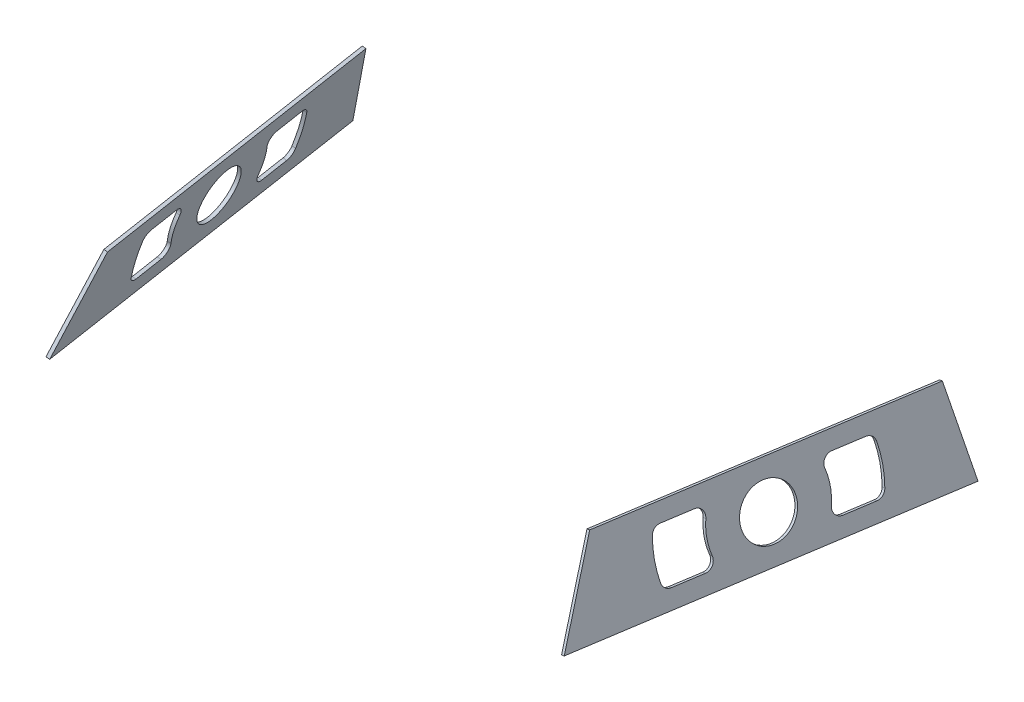
SolidWorks part; units mm, degrees
material "AISI 4130 Steel, normalized at 870C"
ref_plane "Front Plane" through (0, 0, 0) normal (0, 0, 1) x (1, 0, 0)
ref_plane "Top Plane" through (0, 0, 0) normal (0, 1, 0) x (1, 0, 0)
ref_plane "Right Plane" through (0, 0, 0) normal (1, 0, 0) x (0, 0, -1)
ref_plane "Plane1" through (-580.5935, 163.5796, 89.4113) normal (-0.9521, 0.2683, 0.1466) x (0.1411, -0.0398, 0.9892)
sketch "Sketch1" plane through (-580.5935, 163.5796, 89.4113) normal (-0.9521, 0.2683, 0.1466) x (0.1411, -0.0398, 0.9892)
  line L0 (1424.3171, 809.6189) -> (1417.4728, 759.2873)
  line L1 (1417.4728, 759.2873) -> (1634.8983, 768.4219)
  line L2 (1634.8983, 768.4219) -> (1609.6358, 817.4047)
  line L3 (1609.6358, 817.4047) -> (1424.3171, 809.6189)
  line L6 (1409.8147, 798.5353) -> (1433.754, 799.5411) construction
  line L7 (1581.1847, 765.6997) -> (1613.0162, 767.037) construction
  line L9 (1463.8222, 1100.131) -> (1891.0271, 271.7993) construction
  line L10 (1463.8222, 1100.131) -> (1356.2291, 308.913) construction
  line L11 (1591.981, 851.6367) -> (1429.116, 844.9085) construction
  point P4 (1411.0184, 806.0925)
  point P5 (1412.9086, 821.061)
  point P7 (1570.7525, 855.3408)
  point P12 (0, 0)
  point P13 (0, 0)
  point P14 (0, 0)
  point P20 (1510.5485, 848.2726)
  dimension "D1" = 50
  dimension "D2" = 35
extrude "Boss-Extrude1" add sketch "Sketch1" along normal blind 2 from offset 12.7
sketch "Sketch3" plane through (-580.5935, 163.5796, 89.4113) normal (-0.9521, 0.2683, 0.1466) x (0.1411, -0.0398, 0.9892)
  line L0 (1420.895, 784.4531) -> (1622.2671, 792.9133) construction
  line L1 (1424.3171, 809.6189) -> (1417.4728, 759.2873) construction
  line L2 (1634.8983, 768.4219) -> (1609.6358, 817.4047) construction
  line L3 (1516.9765, 813.5118) -> (1526.1856, 763.8546) construction
  line L4 (1609.6358, 817.4047) -> (1424.3171, 809.6189) construction
  line L5 (1417.4728, 759.2873) -> (1634.8983, 768.4219) construction
  circle A0 centre (1521.581, 788.6832) radius 15
  dimension "D1" = 30
extrude "Cut-Extrude4" cut sketch "Sketch3" along normal through all both and the other way through all contours A0
sketch "Sketch4" plane through (-594.5898, 167.523, 91.5668) normal (-0.9521, 0.2683, 0.1466) x (0.1423, -0.0358, 0.9892)
  line L0 (1488.1402, 796.0159) -> (1470.2119, 795.3368)
  line L1 (1489.2757, 766.0374) -> (1471.3474, 765.3583)
  line L2 (1560.3726, 798.7519) -> (1578.3009, 799.4309)
  line L3 (1561.5081, 768.7734) -> (1579.4364, 769.4524)
  line L4 (1612.9968, 810.7523) -> (1427.6475, 803.7317) construction
  line L5 (1489.2757, 766.0374) -> (1561.5081, 768.7734) construction
  line L6 (1420.5955, 753.4288) -> (1638.0568, 761.6656) construction
  line L7 (1488.1402, 796.0159) -> (1560.3726, 798.7519) construction
  arc A1 (1465.4536, 791.0627) -> (1466.2794, 769.2602) centre (1524.8241, 782.3946) ccw
  arc A2 (1556.4529, 774.9197) -> (1555.7968, 792.2407) centre (1524.8241, 782.3946) ccw
  arc A3 (1584.1947, 773.7265) -> (1583.3689, 795.5291) centre (1524.8241, 782.3946) ccw
  arc A4 (1579.4364, 769.4524) -> (1584.1947, 773.7265) centre (1579.2472, 774.4488) ccw
  arc A5 (1578.3009, 799.4309) -> (1583.3689, 795.5291) centre (1578.4902, 794.4345) cw
  arc A9 (1471.3474, 765.3583) -> (1466.2794, 769.2602) centre (1471.1581, 770.3547) cw
  arc A11 (1470.2119, 795.3368) -> (1465.4536, 791.0627) centre (1470.4011, 790.3404) ccw
  arc A12 (1493.1954, 789.8695) -> (1493.8515, 772.5486) centre (1524.8241, 782.3946) ccw
  arc A13 (1489.2757, 766.0374) -> (1493.8515, 772.5486) centre (1489.0865, 771.0338) ccw
  arc A14 (1493.1954, 789.8695) -> (1488.1402, 796.0159) centre (1488.3295, 791.0195) ccw
  arc A15 (1556.4529, 774.9197) -> (1561.5081, 768.7734) centre (1561.3188, 773.7698) ccw
  arc A16 (1555.7968, 792.2407) -> (1560.3726, 798.7519) centre (1560.5618, 793.7554) cw
  circle A20 centre (1524.8241, 782.3946) radius 15 construction
  point P0 (1466.6885, 807.4312)
  point P16 (1583.445, 769.6043)
  point P30 (1467.3388, 765.2065)
  point P36 (1466.2033, 795.185)
  dimension "D1" = 32.5
  dimension "D2" = 120
  dimension "D5" = 5
  dimension "D6" = 32.5
  dimension "D8" = 5
  dimension "D7" = 5
  dimension "D9" = 5
  dimension "D10" = 5
  dimension "D3" = 10
  dimension "D4" = 10
extrude "Cut-Extrude5" cut sketch "Sketch4" against normal through all both and the other way through all
sketch "Sketch5" plane through (-594.5898, 167.523, 91.5668) normal (-0.9521, 0.2683, 0.1466) x (0.1423, -0.0358, 0.9892)
  circle A0 centre (1504.6614, 782.68) radius 20 construction
  circle A1 centre (1504.6614, 782.68) radius 20
  circle A2 centre (1504.662, 782.6522) radius 14.5 construction
  circle A3 centre (1504.662, 782.6522) radius 14.5
split line "Split Line1" [suppressed]
mirror "Mirror2" about plane through (0, 0, 0) normal (1, 0, 0) of bodies 104
